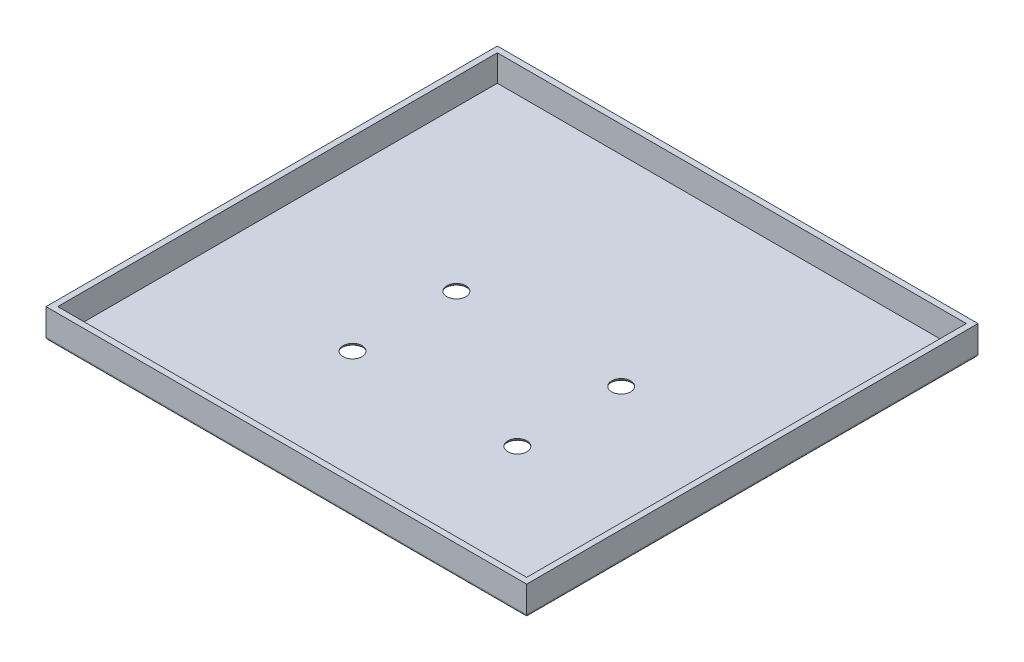
SolidWorks part; units mm, degrees
ref_plane "Front Plane" through (0, 0, 0) normal (0, 0, 1) x (1, 0, 0)
ref_plane "Top Plane" through (0, 0, 0) normal (0, 1, 0) x (1, 0, 0)
ref_plane "Right Plane" through (0, 0, 0) normal (1, 0, 0) x (0, 0, -1)
sketch "Sketch1" plane through (0, 0, 0) normal (0, 1, 0) x (1, 0, 0)
  line L1 (51.3202, -128.8034) -> (-112.6798, -128.8034)
  line L2 (51.3202, -128.8034) -> (51.3202, 25.1966)
  line L3 (51.3202, 25.1966) -> (-112.6798, 25.1966)
  line L4 (-112.6798, -128.8034) -> (-112.6798, 25.1966)
  line L5 (51.3202, -128.8034) -> (-112.6798, 25.1966) construction
  line L6 (51.3202, 25.1966) -> (-112.6798, -128.8034) construction
  circle A5 centre (-56.2295, -45.2236) radius 3.25
  circle A6 centre (0, -45.2236) radius 3.25
  circle A7 centre (-56.2295, -80.6576) radius 3.25
  circle A9 centre (0, -80.6576) radius 3.25
  point P0 (-30.6798, -51.8034)
  dimension "D3" = 6.5
  dimension "D1" = 164
  dimension "D2" = 154
extrude "Boss-Extrude1" add sketch "Sketch1" along normal blind 10
sketch "Sketch2" plane through (0, 10, 0) normal (0, 1, 0) x (1, 0, 0)
  line L0 (-112.6798, -128.8034) -> (51.3202, -128.8034) construction
  line L6 (-110.6798, 23.1966) -> (49.3202, 23.1966)
  line L7 (51.3202, 25.1966) -> (-112.6798, 25.1966) construction
  line L8 (51.3202, -128.8034) -> (51.3202, 25.1966) construction
  line L9 (-112.6798, 25.1966) -> (-112.6798, -128.8034) construction
  line L10 (-110.6798, 23.1966) -> (-110.6798, -126.8034)
  line L11 (-110.6798, -126.8034) -> (49.3202, -126.8034)
  line L12 (49.3202, 23.1966) -> (49.3202, -126.8034)
  line L13 (-110.6798, 23.1966) -> (49.3202, -126.8034) construction
  line L14 (-110.6798, -126.8034) -> (49.3202, 23.1966) construction
  point P0 (-30.6798, -51.8034)
  dimension "D1" = 2
  dimension "D2" = 2
  dimension "D3" = 2
  dimension "D4" = 2
extrude "Cut-Extrude1" cut sketch "Sketch2" along direction (0, 1, 0) on the side against the normal blind 9
fillet "Fillet2" radius 1 8 edges at (-30.6798, 0, 128.8034) (51.3202, 0, 51.8034) (-30.6798, 0, -25.1966) (-112.6798, 0, 51.8034) (0, 0, 83.9076) (-56.2295, 0, 83.9076) (0, 0, 48.4736) (-56.2295, 0, 48.4736)
